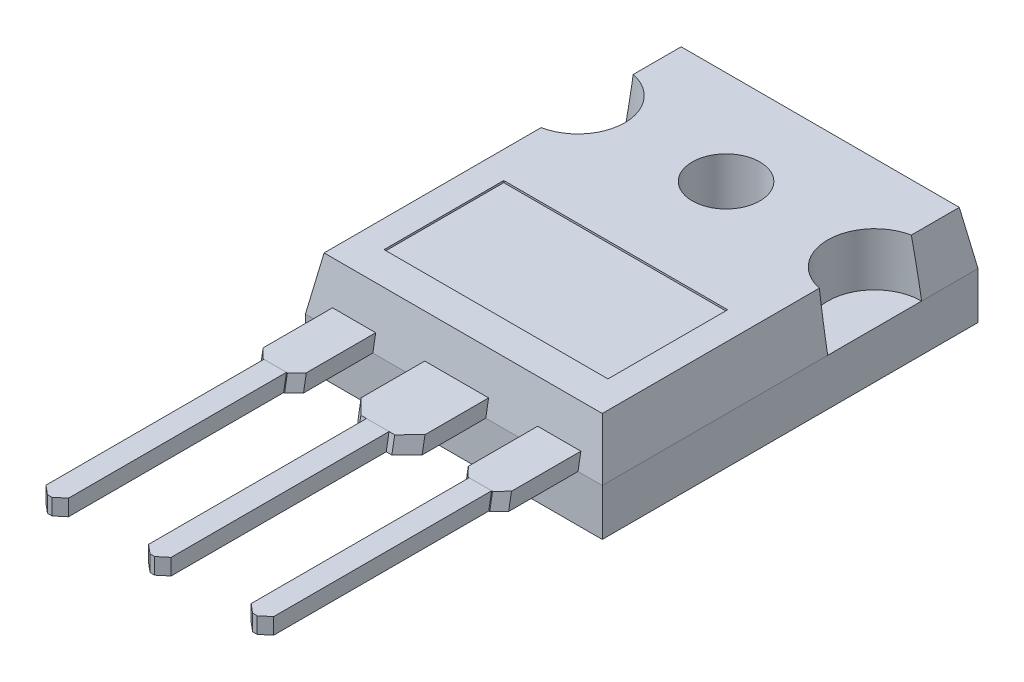
SolidWorks part; units mm, degrees
ref_plane "Front Plane" through (0, 0, 0) normal (0, 0, 1) x (1, 0, 0)
ref_plane "Top Plane" through (0, 0, 0) normal (0, 1, 0) x (1, 0, 0)
ref_plane "Right Plane" through (0, 0, 0) normal (1, 0, 0) x (0, 0, -1)
sketch "Sketch1" plane through (0, 0, 0) normal (0, 1, 0) x (1, 0, 0)
  line L1 (-7.9, 10) -> (7.9, 10)
  line L2 (-7.9, 10) -> (-7.9, -10)
  line L3 (-7.9, -10) -> (7.9, -10)
  line L4 (7.9, 10) -> (7.9, -10)
  line L5 (-7.9, 10) -> (7.9, -10) construction
  line L6 (-7.9, -10) -> (7.9, 10) construction
  point P0 (0, 0)
  dimension "D1" = 15.8
  dimension "D2" = 20
extrude "Boss-Extrude1" add sketch "Sketch1" along normal blind 2.49
sketch "Sketch2" plane through (0, 2.49, 0) normal (0, 1, 0) x (1, 0, 0)
  line L1 (-7.9, -10) -> (7.9, -10)
  line L2 (-7.9, -10) -> (-7.9, 10)
  line L3 (-7.9, 10) -> (7.9, 10)
  line L4 (7.9, -10) -> (7.9, 10)
  line L5 (-7.9, -10) -> (7.9, 10) construction
  line L6 (-7.9, 10) -> (7.9, -10) construction
  point P0 (0, 0)
extrude "Boss-Extrude3" add sketch "Sketch2" along normal blind 2.82 draft 10
sketch "Sketch4" plane through (0, 0, 0) normal (0, 0, 1) x (1, 0, 0)
  line L0 (0, 0) -> (0, 5.31) construction
  line L1 (-7.4028, 5.31) -> (7.4028, 5.31) construction
  line L2 (-7.9, 2.49) -> (7.9, 2.49) construction
  line L3 (-1.7, 3.35) -> (1.7, 3.35)
  line L4 (-1.7, 3.35) -> (-1.7, 2.49)
  line L5 (-1.7, 2.49) -> (1.7, 2.49)
  line L6 (1.7, 3.35) -> (1.7, 2.49)
  line L7 (-1.7, 3.35) -> (1.7, 2.49) construction
  line L8 (-1.7, 2.49) -> (1.7, 3.35) construction
  line L9 (-6.61, 3.35) -> (-6.61, 2.49)
  line L10 (4.31, 3.35) -> (6.61, 3.35)
  line L11 (4.31, 3.35) -> (4.31, 2.49)
  line L12 (4.31, 2.49) -> (6.61, 2.49)
  line L13 (6.61, 3.35) -> (6.61, 2.49)
  line L14 (4.31, 3.35) -> (6.61, 2.49) construction
  line L15 (4.31, 2.49) -> (6.61, 3.35) construction
  line L16 (-4.31, 2.49) -> (-6.61, 2.49)
  line L17 (-4.31, 3.35) -> (-4.31, 2.49)
  line L18 (-4.31, 3.35) -> (-6.61, 3.35)
  point P5 (0, 2.92)
  point P12 (5.46, 2.92)
  dimension "D1" = 3.4
  dimension "D2" = 0.86
  dimension "D3" = 5.46
  dimension "D4" = 2.3
extrude "Boss-Extrude4" add sketch "Sketch4" along normal blind 4.2 from surface starting at face at (0, 3.9, 9.7514)
sketch "Sketch5" plane through (0, 0, 0) normal (0, 0, 1) x (1, 0, 0)
  line L0 (1.7, 2.49) -> (-1.7, 2.49) construction
  line L1 (5.46, 0) -> (5.46, 5.31) construction
  line L2 (-0.6, 3.35) -> (0.6, 3.35)
  line L3 (-0.6, 3.35) -> (-0.6, 2.49)
  line L4 (-0.6, 2.49) -> (0.6, 2.49)
  line L5 (0.6, 3.35) -> (0.6, 2.49)
  line L6 (-0.6, 3.35) -> (0.6, 2.49) construction
  line L7 (-0.6, 2.49) -> (0.6, 3.35) construction
  line L8 (0, 0) -> (0, 5.31) construction
  line L9 (-7.4028, 5.31) -> (7.4028, 5.31) construction
  line L10 (6.61, 2.49) -> (4.31, 2.49) construction
  line L11 (4.86, 3.35) -> (6.06, 3.35)
  line L12 (4.86, 3.35) -> (4.86, 2.49)
  line L13 (4.86, 2.49) -> (6.06, 2.49)
  line L14 (6.06, 3.35) -> (6.06, 2.49)
  line L15 (4.86, 3.35) -> (6.06, 2.49) construction
  line L16 (4.86, 2.49) -> (6.06, 3.35) construction
  line L17 (-7.9, 0) -> (7.9, 0) construction
  line L18 (-4.86, 3.35) -> (-4.86, 2.49)
  line L19 (-4.86, 3.35) -> (-6.06, 3.35)
  line L20 (-6.06, 3.35) -> (-6.06, 2.49)
  line L21 (-4.86, 2.49) -> (-6.06, 2.49)
  point P0 (0, 2.92)
  point P12 (5.46, 2.92)
  dimension "D1" = 1.2
  dimension "D2" = 1.2
extrude "Boss-Extrude6" add sketch "Sketch5" along normal blind 12 from vertex separate body starting at point (6.61, 3.35, 14.0484)
sketch "Sketch6" plane through (0, 5.31, 0) normal (0, 1, 0) x (1, 0, 0)
  circle A0 centre (0, 4.49) radius 1.8
  dimension "D2" = 3.6
  dimension "D1" = 5.51
extrude "Cut-Extrude1" cut sketch "Sketch6" against normal through all
sketch "Sketch7" plane through (0, 5.31, 0) normal (0, 1, 0) x (1, 0, 0)
  line L0 (0, 0) -> (0, 10) construction
  line L1 (7.9, 10) -> (-7.9, 10) construction
  line L3 (7.9, -10) -> (7.9, 10) construction
  circle A0 centre (7.9, 4.5) radius 2.5
  circle A1 centre (-7.9, 4.5) radius 2.5
  dimension "D2" = 5
  dimension "D1" = 5.5
extrude "Cut-Extrude2" cut sketch "Sketch7" against normal up to vertex (2.82 mm away) up to point (7.9, 2.49, 10)
chamfer "Chamfer2" distance 0.5 angle 45 4 edges at (6.61, 2.92, 14.1242) (4.31, 2.92, 14.1242) (-4.31, 2.92, 14.1242) (-6.61, 2.92, 14.1242)
chamfer "Chamfer3" distance 0.8 angle 45 2 edges at (1.7, 2.92, 14.1242) (-1.7, 2.92, 14.1242)
chamfer "Chamfer7" distance 0.4 angle 50 2 edges at (0.6, 2.92, 26.0484) (-0.6, 2.92, 26.0484) first distance on face at (0.6, 2.92, 20.0484) first distance on face at (-0.6, 2.92, 20.0484)
chamfer "Chamfer8" distance 0.4 angle 50 2 edges at (-4.86, 2.92, 26.0484) (-6.06, 2.92, 26.0484) first distance on face at (-4.86, 2.92, 20.0484) first distance on face at (-6.06, 2.92, 20.0484)
chamfer "Chamfer9" distance 0.4 angle 50 2 edges at (6.06, 2.92, 26.0484) (4.86, 2.92, 26.0484) first distance on face at (6.06, 2.92, 20.0484) first distance on face at (4.86, 2.92, 20.0484)
sketch "Sketch9" plane through (0, 0, 0) normal (0, -1, 0) x (1, 0, 0)
  line L1 (-6.4932, 7.0481) -> (6.4932, 7.0481)
  line L2 (-6.4932, 7.0481) -> (-6.4932, -8.3924)
  line L3 (-6.4932, -8.3924) -> (6.4932, -8.3924)
  line L4 (6.4932, 7.0481) -> (6.4932, -8.3924)
  line L5 (-6.4932, 7.0481) -> (6.4932, -8.3924) construction
  line L6 (-6.4932, -8.3924) -> (6.4932, 7.0481) construction
  point P0 (0, -0.6721)
extrude "Cut-Extrude3" cut sketch "Sketch9" against normal up to vertex (2.49 mm away) up to point (7.9, 2.49, -2)
sketch "Sketch10" plane through (0, 2.49, 0) normal (0, -1, 0) x (1, 0, 0)
  line L1 (-6.4932, 7.0481) -> (6.4932, 7.0481)
  line L2 (-6.4932, 7.0481) -> (-6.4932, -8.3924)
  line L3 (-6.4932, -8.3924) -> (6.4932, -8.3924)
  line L4 (6.4932, 7.0481) -> (6.4932, -8.3924)
extrude "Boss-Extrude7" add sketch "Sketch10" along normal up to surface (2.49 mm away) up to face at (0, 0, -0.6721)
sketch "Sketch13" plane through (0, 2.49, 0) normal (0, 1, 0) x (1, 0, 0)
  circle A0 centre (0, 4.49) radius 1.8
extrude "Cut-Extrude4" cut sketch "Sketch13" against normal up to surface (2.49 mm away) up to face at (0, 0, 0)
sketch "Sketch14" plane through (0, 5.31, 0) normal (0, 1, 0) x (1, 0, 0)
  line L1 (-5.9596, -1.3833) -> (5.9596, -1.3833)
  line L2 (-5.9596, -1.3833) -> (-5.9596, -7.7559)
  line L3 (-5.9596, -7.7559) -> (5.9596, -7.7559)
  line L4 (5.9596, -1.3833) -> (5.9596, -7.7559)
  line L5 (-5.9596, -1.3833) -> (5.9596, -7.7559) construction
  line L6 (-5.9596, -7.7559) -> (5.9596, -1.3833) construction
  point P0 (0, -4.5696)
extrude "Cut-Extrude5" cut sketch "Sketch14" against normal blind 0.1
